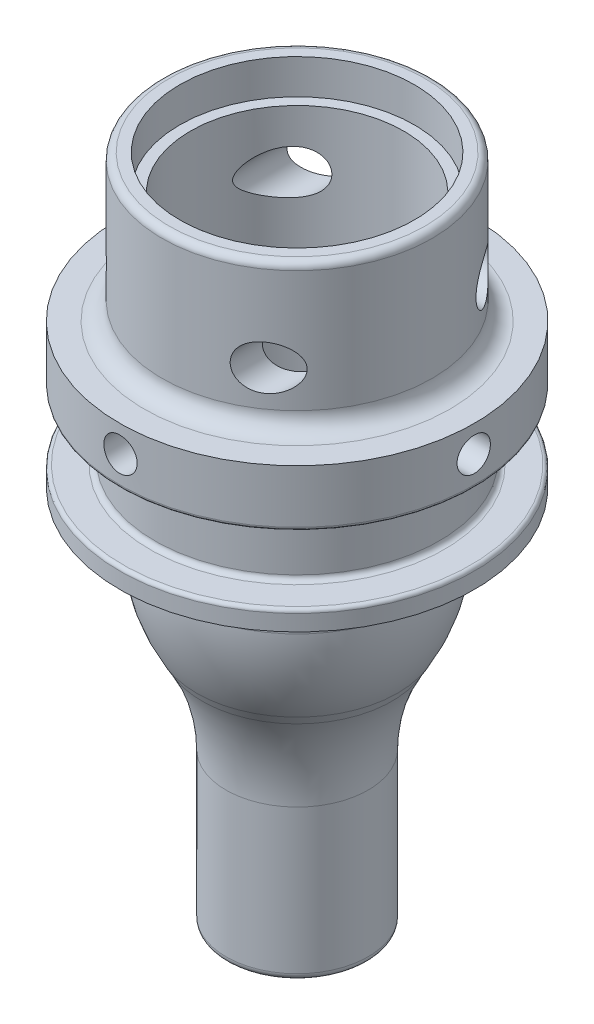
SolidWorks part; units mm, degrees
material "Brass"
ref_plane "Front Plane" through (0, 0, 0) normal (0, 0, 1) x (1, 0, 0)
ref_plane "Top Plane" through (0, 0, 0) normal (0, 1, 0) x (1, 0, 0)
ref_plane "Right Plane" through (0, 0, 0) normal (1, 0, 0) x (0, 0, -1)
sketch "Sketch1" plane through (0, 0, 0) normal (0, 0, 1) x (1, 0, 0)
  line L0 (4.826, 23.876) -> (4.826, 18.6563)
  line L2 (6.3373, 17.3228) -> (6.3373, 16.7513)
  line L3 (6.3373, 13.5128) -> (5.0673, 13.5128)
  line L5 (4.445, 10.4116) -> (2.54, 7.112)
  line L6 (2.54, 7.112) -> (2.54, 0)
  line L7 (2.54, 0) -> (2.032, 0)
  line L8 (2.032, 0) -> (2.032, 7.332)
  line L9 (2.032, 7.332) -> (3.81, 10.4116)
  line L10 (3.81, 10.4116) -> (3.81, 22.6314)
  line L11 (4.191, 23.876) -> (4.826, 23.876)
  line L12 (0, 20.955) -> (0, 0) construction
  line L13 (6.2103, 16.6243) -> (5.2578, 16.6243)
  line L14 (5.08, 16.4465) -> (5.08, 14.3891)
  line L15 (5.2578, 14.2113) -> (6.2103, 14.2113)
  line L16 (5.08, 13.5128) -> (5.08, 17.3228) construction
  line L17 (6.3373, 14.0843) -> (6.3373, 13.5128)
  line L18 (5.0673, 13.5128) -> (4.445, 13.5128)
  line L19 (4.445, 13.5128) -> (4.445, 10.4116)
  line L20 (6.3373, 17.3228) -> (6.3373, 18.6563)
  line L21 (6.3373, 18.6563) -> (4.826, 18.6563)
  line L22 (4.191, 23.876) -> (4.191, 22.6314)
  line L23 (4.191, 22.6314) -> (3.81, 22.6314)
  arc A0 (6.2103, 14.2113) -> (6.3373, 14.0843) centre (6.2103, 14.0843) cw
  arc A1 (6.2103, 16.6243) -> (6.3373, 16.7513) centre (6.2103, 16.7513) ccw
  arc A2 (5.08, 14.3891) -> (5.2578, 14.2113) centre (5.2578, 14.3891) ccw
  arc A3 (5.2578, 16.6243) -> (5.08, 16.4465) centre (5.2578, 16.4465) ccw
  point P20 (5.08, 15.4178)
  point P36 (6.3373, 14.2113)
  point P41 (5.08, 14.2113)
  point P44 (5.08, 16.6243)
  dimension "D14" = 0.127
  dimension "D15" = 0.1778
  dimension "D1" = 6.3373
  dimension "D3" = 0.6985
  dimension "D4" = 7.112
  dimension "D5" = 0.508
  dimension "D6" = 30
  dimension "D7" = 10.3632
  dimension "D8" = 2.54
  dimension "D9" = 1.27
  dimension "D10" = 2.413
  dimension "D11" = 5.08
  dimension "D12" = 0.635
  dimension "D13" = 150
  dimension "D16" = 20.955
  dimension "D17" = 1.016
  dimension "D18" = 3.81
  dimension "D19" = 2.032
  dimension "D20" = 1.2446
  dimension "D21" = 0.381
  dimension "D22" = 23.876
revolve "Revolve1" add sketch "Sketch1" angle 360 about L12
sketch "Sketch2" plane through (0, 0, 0) normal (0, 0, 1) x (1, 0, 0)
  line L0 (3.81, 23.876) -> (-3.81, 23.876) construction
  point P0 (2.794, 20.574)
  dimension "D1" = 3.302
  dimension "D2" = 2.794
hole_wizard "1/16 (0.0625) Diameter Hole1" positions "Sketch2" profile "Sketch3" hole size "1/16" standard "ANSI Inch" end condition through all
sketch "Sketch3" plane through (2.794, 20.574, 0) normal (1, 0, 0) x (0, 1, 0)
  line L0 (0, 0) -> (0, 6.3373)
  line L1 (0, 6.3373) -> (0.7937, 6.3373)
  line L2 (0.7937, 6.3373) -> (0.7937, 0)
  line L5 (0.7937, 0) -> (0, 0)
  line L11 (0, -6.35) -> (0, 107.95) construction
  dimension "Thru Hole Dia." = 1.5875
  dimension "Thru Hole Depth" = 6.3373
pattern_circular "CirPattern1" count 4 over 360 about axis through (0, 20.955, 0) along (0, 1, 0) of "1/16 (0.0625) Diameter Hole1" reverse direction yes
ref_plane "Plane1" through (0, 0, 6.3373) normal (0, 0, 1) x (1, 0, 0)
sketch "Sketch5" plane through (0, 0, 6.3373) normal (0, 0, 1) x (1, 0, 0)
  line L0 (0, 16.7513) -> (0, 18.6563) construction
  line L1 (6.3373, 18.6563) -> (-6.3373, 18.6563) construction
  line L2 (-6.3373, 16.7513) -> (6.3373, 16.7513) construction
  point P0 (0, 17.7038)
  point P8 (0, 17.7038)
hole_wizard "#0-80 Tapped Hole1" positions "Sketch5" profile "Sketch7" tap size "#0-80" standard "ANSI Inch"
sketch "Sketch7" plane through (0, 17.7038, 6.3373) normal (1, 0, 0) x (0, -1, 0)
  line L0 (0, 0) -> (0, 2.1359)
  line L1 (0, 2.1359) -> (0.5956, 1.778)
  line L2 (0.5956, 1.778) -> (0.5956, 0)
  line L5 (0.5956, 0) -> (0, 0)
  line L10 (0, 2.1359) -> (-0.5956, 1.778) construction
  line L11 (0, -6.35) -> (0, 107.95) construction
  dimension "Tap Drill Dia." = 1.1913
  dimension "Tap Drill Depth" = 1.778
  dimension "Drill Angle" = 118
cosmetic thread "Hole Thread2" parameters "D1"=1.778, "D2"=1.524
pattern_circular "CirPattern2" count 4 over 360 of "#0-80 Tapped Hole1" reverse direction yes
cosmetic thread "Hole Thread3" parameters "D1"=1.778, "D2"=1.524
cosmetic thread "Hole Thread4" parameters "D1"=1.778, "D2"=1.524
cosmetic thread "Hole Thread5" parameters "D1"=1.778, "D2"=1.524
fillet "Fillet1" radius 0.254 1 edges at (-4.826, 23.876, 0)
fillet "Fillet2" radius 6.35 2 edges at (-3.81, 10.4116, 0) (-2.032, 7.332, 0)
fillet "Fillet3" radius 6.35 2 edges at (-4.445, 10.4116, 0) (-2.54, 7.112, 0)
fillet "Fillet4" radius 0.635 1 edges at (-4.826, 18.6563, 0)
fillet "Fillet5" radius 0.254 2 edges at (-2.032, 0, 0) (-2.54, 0, 0)
fillet "Fillet6" radius 0.762 1 edges at (-4.445, 13.5128, 0)
